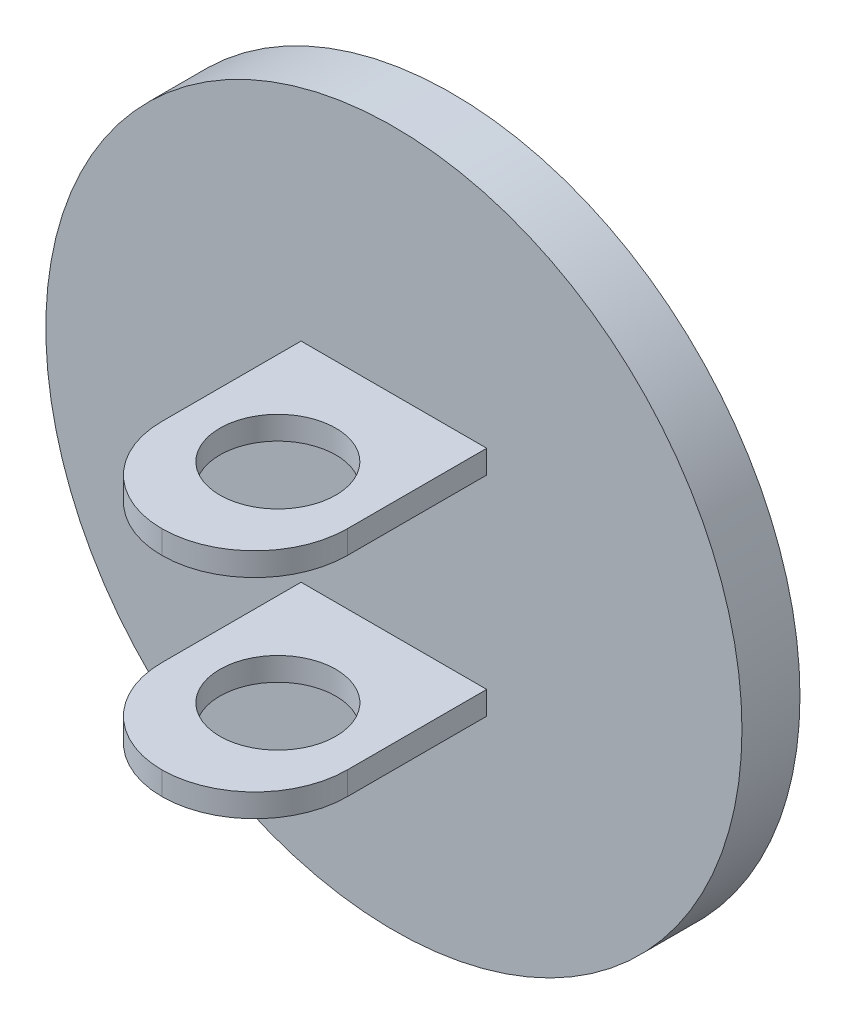
SolidWorks part; units mm, degrees
ref_plane "Front Plane" through (0, 0, 0) normal (0, 0, 1) x (1, 0, 0)
ref_plane "Top Plane" through (0, 0, 0) normal (0, 1, 0) x (1, 0, 0)
ref_plane "Right Plane" through (0, 0, 0) normal (1, 0, 0) x (0, 0, -1)
sketch "Sketch1" plane through (0, 0, 0) normal (0, 0, 1) x (1, 0, 0)
  circle A0 centre (0, 0) radius 25
  dimension "D1" = 50
extrude "Boss-Extrude1" add sketch "Sketch1" along normal blind 35
sketch "Sketch2" plane through (0, 0, 35) normal (0, 0, 1) x (1, 0, 0)
  circle A0 centre (0, 0) radius 150
  dimension "D1" = 300
extrude "Boss-Extrude2" add sketch "Sketch2" along normal blind 25
sketch "Sketch3" plane through (0, 0, 60) normal (0, 0, 1) x (1, 0, 0)
  line L1 (-40, 50) -> (40, 50)
  line L2 (-40, 50) -> (-40, -50)
  line L3 (-40, -50) -> (40, -50)
  line L4 (40, 50) -> (40, -50)
  line L5 (-40, 50) -> (40, -50) construction
  line L6 (-40, -50) -> (40, 50) construction
  line L7 (-40, 40) -> (40, 40)
  line L8 (-40, 40) -> (-40, -40)
  line L9 (-40, -40) -> (40, -40)
  line L10 (40, 40) -> (40, -40)
  line L11 (-40, 40) -> (40, -40) construction
  line L12 (-40, -40) -> (40, 40) construction
  point P0 (0, 0)
  point P6 (0, 0)
  dimension "D1" = 100
  dimension "D2" = 80
  dimension "D3" = 80
extrude "Boss-Extrude3" add sketch "Sketch3" along normal blind 100 contours L9 L2 L3 L4 | L2 L7 L4 L1 region at (0, 45, 60) region at (0, -45, 60)
sketch "Sketch4" plane through (0, -50, 0) normal (0, -1, 0) x (1, 0, 0)
  line L0 (0, 160) -> (0, 60) construction
  line L1 (-40, 160) -> (40, 160) construction
  line L2 (150, 60) -> (-150, 60) construction
  circle A0 centre (0, 110) radius 25
  dimension "D1" = 50
extrude "Cut-Extrude1" cut sketch "Sketch4" against normal through all
fillet "Fillet1" radius 40 4 edges at (40, -45, 160) (40, 45, 160) (-40, 45, 160) (-40, -45, 160)
